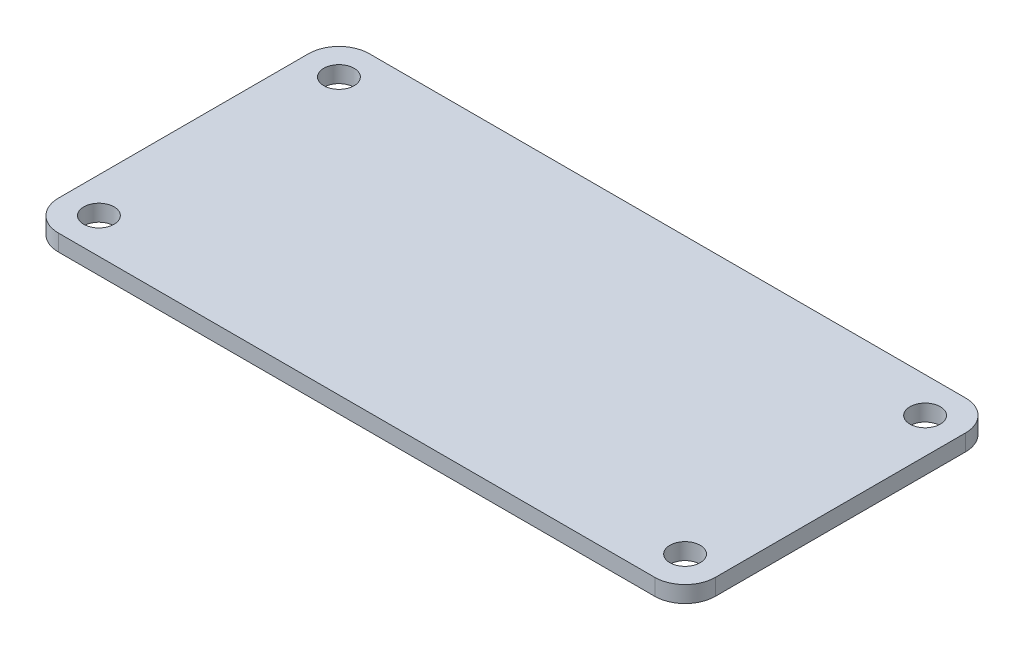
SolidWorks part; units mm, degrees
ref_plane "前视基准面" through (0, 0, 0) normal (0, 0, 1) x (1, 0, 0)
ref_plane "上视基准面" through (0, 0, 0) normal (0, 1, 0) x (1, 0, 0)
ref_plane "右视基准面" through (0, 0, 0) normal (1, 0, 0) x (0, 0, -1)
sketch "草图1" plane through (0, 0, 0) normal (0, 1, 0) x (1, 0, 0)
  line L1 (-29.5, 15.375) -> (29.5, 15.375)
  line L2 (-32.5, 12.375) -> (-32.5, -12.375)
  line L3 (-29.5, -15.375) -> (29.5, -15.375)
  line L4 (32.5, 12.375) -> (32.5, -12.375)
  line L5 (-32.5, 15.375) -> (32.5, -15.375) construction
  line L6 (-32.5, -15.375) -> (32.5, 15.375) construction
  arc A0 (-32.5, -12.375) -> (-29.5, -15.375) centre (-29.5, -12.375) ccw
  arc A1 (29.5, -15.375) -> (32.5, -12.375) centre (29.5, -12.375) ccw
  arc A2 (29.5, 15.375) -> (32.5, 12.375) centre (29.5, 12.375) cw
  arc A3 (-29.5, 15.375) -> (-32.5, 12.375) centre (-29.5, 12.375) ccw
  point P0 (0, 0)
  dimension "D3" = 3
  dimension "D1" = 30.75
  dimension "D2" = 65
extrude "凸台-拉伸1" add sketch "草图1" along normal blind 1.63
sketch "草图2" plane through (0, 1.63, 0) normal (0, 1, 0) x (1, 0, 0)
  line L0 (29.5, 15.375) -> (-29.5, 15.375) construction
  line L2 (-32.5, 12.375) -> (-32.5, -12.375) construction
  line L3 (-29.5, -15.375) -> (29.5, -15.375) construction
  line L4 (32.5, -12.375) -> (32.5, 12.375) construction
  circle A0 centre (-29, 11.875) radius 1.5
  circle A1 centre (-29, -11.875) radius 1.5
  circle A2 centre (29, -11.875) radius 1.5
  circle A3 centre (29, 11.875) radius 1.5
  dimension "D1" = 3
  dimension "D2" = 3.5
  dimension "D3" = 3.5
  dimension "D4" = 3.5
  dimension "D5" = 3.5
extrude "切除-拉伸1" cut sketch "草图2" against normal through all
sketch "草图8" plane through (0, 0, 0) normal (0, -1, 0) x (1, 0, 0)
  line L0 (29.5, -15.375) -> (-29.5, -15.375) construction
  line L1 (-25.7, -8.735) -> (25.3, -8.735)
  line L2 (-25.7, -8.735) -> (-25.7, -13.735)
  line L3 (-25.7, -13.735) -> (25.3, -13.735)
  line L4 (25.3, -8.735) -> (25.3, -13.735)
  line L5 (32.5, 12.375) -> (32.5, -12.375) construction
  dimension "D1" = 5
  dimension "D2" = 51
  dimension "D3" = 1.64
  dimension "D4" = 7.2
extrude "凸台-拉伸6" add sketch "草图8" along normal blind 3.68
sketch "草图9" plane through (0, 1.63, 0) normal (0, 1, 0) x (1, 0, 0)
  line L0 (-29.5, -15.375) -> (29.5, -15.375) construction
  line L1 (-10.1894, -15.375) -> (9.318, -15.375)
  line L2 (-10.1894, -15.375) -> (-10.1894, -9.2845)
  line L3 (-10.1894, -9.2845) -> (9.318, -9.2845)
  line L4 (9.318, -15.375) -> (9.318, -9.2845)
